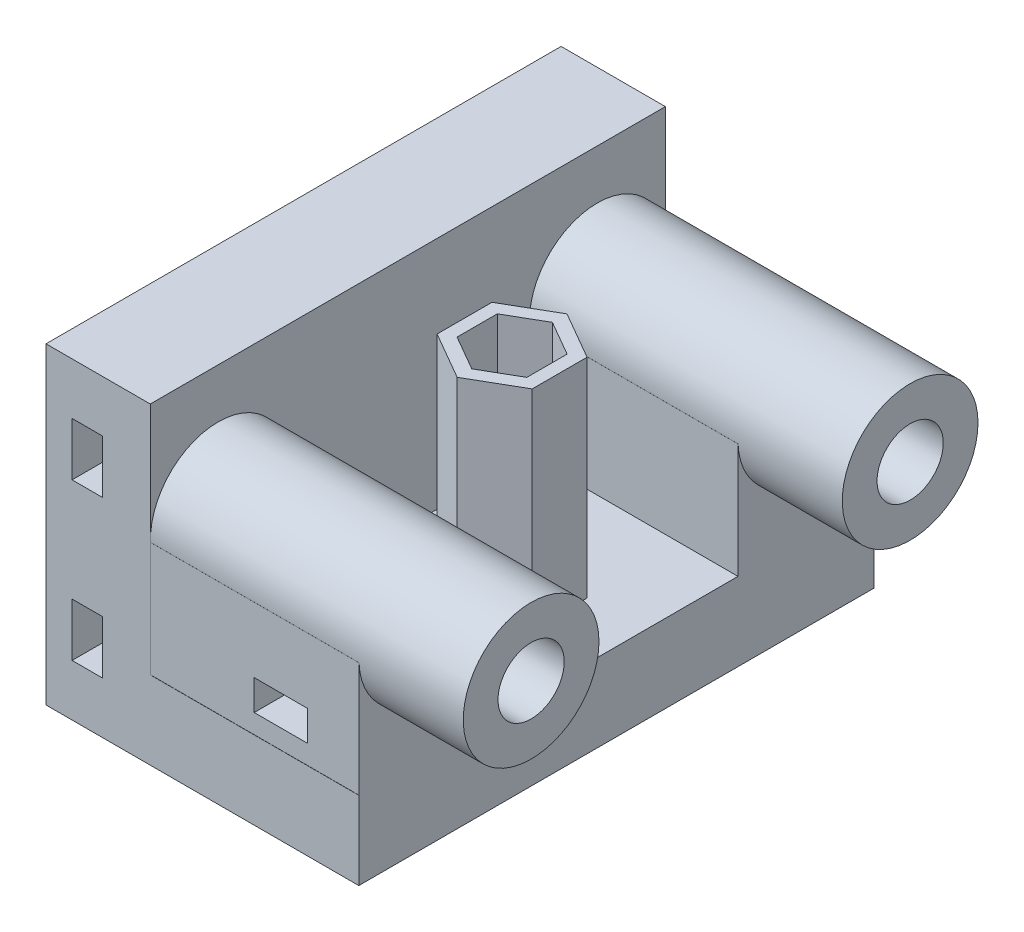
SolidWorks part; units mm, degrees
ref_plane "Front Plane" through (0, 0, 0) normal (0, 0, 1) x (1, 0, 0)
ref_plane "Top Plane" through (0, 0, 0) normal (0, 1, 0) x (1, 0, 0)
ref_plane "Right Plane" through (0, 0, 0) normal (1, 0, 0) x (0, 0, -1)
sketch "Sketch1" plane through (0, 0, 0) normal (1, 0, 0) x (0, 0, -1)
  line L1 (0, 0) -> (88.9, 0)
  line L2 (0, 0) -> (0, 76.2)
  line L3 (0, 76.2) -> (88.9, 76.2)
  line L4 (88.9, 0) -> (88.9, 76.2)
  dimension "D1" = 76.2
  dimension "D2" = 88.9
extrude "Boss-Extrude1" add sketch "Sketch1" along normal blind 25.4
sketch "Sketch2" plane through (0, 0, 0) normal (-1, 0, 0) x (0, 0, 1)
  line L0 (-88.9, 0) -> (-88.9, 76.2) construction
  line L1 (-80.264, 19.05) -> (-88.9, 19.05) construction
  line L2 (-80.264, 57.15) -> (-88.9, 57.15) construction
  line L3 (-44.45, 76.2) -> (-44.45, 0) construction
  line L4 (-88.9, 76.2) -> (0, 76.2) construction
  line L5 (0, 0) -> (-88.9, 0) construction
  circle A0 centre (-80.264, 57.15) radius 4.1021
  circle A1 centre (-80.264, 19.05) radius 4.1021
  circle A2 centre (-8.636, 19.05) radius 4.1021
  circle A3 centre (-8.636, 57.15) radius 4.1021
  dimension "D2" = 8.2042
  dimension "d1" = 19.05
  dimension "D3" = 8.636
  dimension "D4" = 38.1
extrude "Cut-Extrude1" cut sketch "Sketch2" against normal blind 19.05 contours A1 | A3 | A2 | A0 region at (0, 19.05, -80.264) region at (0, 19.05, -8.636) region at (0, 57.15, -8.636)
sketch "Sketch3" plane through (0, 0, 0) normal (0, 0, 1) x (1, 0, 0)
  line L0 (0, 61.2521) -> (0, 53.0479) construction
  line L1 (0, 57.15) -> (13.716, 57.15) construction
  line L2 (6.35, 63.627) -> (13.716, 63.627)
  line L3 (6.35, 63.627) -> (6.35, 50.673)
  line L4 (6.35, 50.673) -> (13.716, 50.673)
  line L5 (0, 38.1) -> (25.4, 38.1) construction
  line L6 (0, 76.2) -> (0, 0) construction
  line L7 (25.4, 76.2) -> (25.4, 0) construction
  line L8 (13.716, 12.573) -> (13.716, 25.527)
  line L9 (0, 61.2521) -> (0, 53.0479)
  line L11 (6.35, 25.527) -> (13.716, 25.527)
  line L12 (13.716, 63.627) -> (13.716, 50.673)
  line L13 (6.35, 12.573) -> (6.35, 25.527)
  line L14 (6.35, 12.573) -> (13.716, 12.573)
  dimension "D1" = 7.366
  dimension "D2" = 12.954
  dimension "D3" = 6.35
extrude "Cut-Extrude2" cut sketch "Sketch3" against normal blind 15.24 contours L12 L2 L3 L4 | L13 L14 L8 L11 region at (10.033, 57.15, 0) region at (10.033, 19.05, 0)
ref_plane "Plane1" through (0, 0, -44.45) normal (0, 0, 1) x (1, 0, 0)
mirror "Mirror1" about plane through (0, 0, -44.45) normal (0, 0, 1) of "Cut-Extrude2"
sketch "Sketch5" plane through (25.4, 0, 0) normal (1, 0, 0) x (0, 0, -1)
  line L0 (88.9, 0) -> (88.9, 76.2) construction
  line L1 (0, 0) -> (88.9, 0)
  line L2 (0, 0) -> (0, 19.05)
  line L3 (0, 19.05) -> (88.9, 19.05)
  line L4 (88.9, 0) -> (88.9, 19.05)
  dimension "D1" = 19.05
extrude "Boss-Extrude2" add sketch "Sketch5" along normal blind 50.8
sketch "Sketch6" plane through (25.4, 0, 0) normal (1, 0, 0) x (0, 0, -1)
  line L0 (-1.7145, 47.625) -> (90.6145, 47.625) construction
  line L3 (44.45, 76.2) -> (44.45, 19.05) construction
  line L4 (88.9, 76.2) -> (0, 76.2) construction
  line L5 (88.9, 19.05) -> (0, 19.05) construction
  line L6 (-1.7145, 47.625) -> (-1.7145, 64.1562) construction
  circle A0 centre (-1.7145, 47.625) radius 8.0645
  circle A1 centre (-1.7145, 47.625) radius 16.5312
  circle A2 centre (90.6145, 47.625) radius 8.0645
  circle A3 centre (90.6145, 47.625) radius 16.5312
  point P8 (44.45, 47.625)
  point P9 (44.45, 47.625)
  dimension "D2" = 16.129
  dimension "D3" = 8.4667
  dimension "D5" = 33.0623
  dimension "D4" = 16.5312
  dimension "V2" = 92.329
extrude "Boss-Extrude3" add sketch "Sketch6" along normal blind 76.2
sketch "Sketch7" plane through (0, 0, 0) normal (0, 0, 1) x (1, 0, 0)
  line L0 (25.4, 19.05) -> (25.4, 0)
  line L9 (25.4, 31.183) -> (25.4, 39.7449)
  line L10 (0, 76.2) -> (0, 0)
  line L11 (0, 0) -> (76.2, 0)
  line L12 (76.2, 0) -> (76.2, 19.05)
  line L13 (76.2, 19.05) -> (25.4, 19.05)
  line L14 (25.4, 19.05) -> (25.4, 31.183)
  line L15 (25.4, 31.183) -> (25.4, 39.7449)
  line L16 (25.4, 39.7449) -> (25.4, 55.5051)
  line L17 (25.4, 39.7449) -> (25.4, 55.5051)
  line L19 (25.4, 76.2) -> (0, 76.2)
  line L20 (0, 76.2) -> (0, 0)
  line L21 (0, 0) -> (76.2, 0)
  line L22 (76.2, 0) -> (76.2, 19.05)
  line L23 (76.2, 19.05) -> (25.4, 19.05)
  line L24 (25.4, 19.05) -> (25.4, 31.183)
  line L26 (25.4, 55.5051) -> (25.4, 64.067)
  line L27 (25.4, 55.5051) -> (25.4, 64.067)
  line L28 (25.4, 64.067) -> (25.4, 76.2)
  line L29 (25.4, 76.2) -> (0, 76.2)
  line L30 (25.4, 64.067) -> (25.4, 76.2)
  line M11 (13.716, 63.627) -> (13.716, 50.673)
  line M12 (13.716, 50.673) -> (6.35, 50.673)
  line M13 (6.35, 50.673) -> (6.35, 63.627)
  line M14 (6.35, 63.627) -> (13.716, 63.627)
  line M15 (0, 76.2) -> (0, 0)
  line M16 (0, 0) -> (76.2, 0)
  line M17 (76.2, 0) -> (76.2, 19.05)
  line M18 (76.2, 19.05) -> (25.4, 19.05)
  line M19 (25.4, 19.05) -> (25.4, 31.183)
  line M20 (25.4, 31.183) -> (25.4, 39.7449)
  line M21 (25.4, 39.7449) -> (25.4, 55.5051)
  line M22 (25.4, 55.5051) -> (25.4, 64.067)
  line M23 (25.4, 64.067) -> (25.4, 76.2)
  line M24 (25.4, 76.2) -> (0, 76.2)
  line M25 (6.35, 12.573) -> (6.35, 25.527)
  line M26 (6.35, 25.527) -> (13.716, 25.527)
  line M27 (13.716, 25.527) -> (13.716, 12.573)
  line M28 (13.716, 12.573) -> (6.35, 12.573)
  dimension "D1" = 0
extrude "Boss-Extrude4" add sketch "Sketch7" along normal blind 18.288 contours L0 M18 M16 M17 | L0 M19 M20 M21 M22 M23 M24 M15 M16 M28 M25 M26 M27 M14 M11 M12 M13 region at (50.8, 9.525, 0) region at (12.9917, 38.1, 0)
mirror "Mirror2" about plane through (0, 0, -44.45) normal (0, 0, 1) of "Boss-Extrude4"
sketch "Sketch8" plane through (0, 19.05, 0) normal (0, 1, 0) x (1, 0, 0)
  line L0 (101.6, 14.8167) -> (25.4, 14.8167) construction
  line L1 (25.4, -18.2457) -> (101.6, -18.2457) construction
  line L2 (101.6, 14.8167) -> (25.4, 14.8167)
  line L3 (25.4, -18.2457) -> (101.6, -18.2457)
  line L4 (25.4, 107.188) -> (25.4, -18.288)
  line L5 (25.4, -18.288) -> (76.2, -18.288)
  line L6 (76.2, -18.288) -> (76.2, 107.188)
  line L7 (76.2, 107.188) -> (25.4, 107.188)
  line L8 (25.4, 107.188) -> (25.4, -18.288)
  line L9 (25.4, -18.288) -> (76.2, -18.288)
  line L10 (76.2, -18.288) -> (76.2, 107.188)
  line L11 (76.2, 107.188) -> (25.4, 107.188)
  line L13 (25.4, 14.8167) -> (76.2, 14.8167)
  line L14 (25.4, 14.8167) -> (25.4, -18.2457)
  line L15 (25.4, -18.2457) -> (76.2, -18.2457)
  line L16 (76.2, 14.8167) -> (76.2, -18.2457)
  line M5 (25.4, 107.188) -> (25.4, -18.288)
  line M7 (76.2, -18.288) -> (76.2, 107.188)
  dimension "D1" = 0
extrude "Boss-Extrude5" add sketch "Sketch8" along normal blind 27.94 contours L3 L2 M5 M7 region at (50.8, 19.05, 1.7145)
sketch "Sketch11" plane through (101.6, 0, 0) normal (1, 0, 0) x (0, 0, -1)
  circle A0 centre (-1.7145, 47.625) radius 8.0645
  circle A1 centre (-1.7145, 47.625) radius 8.0645 construction
extrude "Cut-Extrude5" cut sketch "Sketch11" against normal blind 76.2
sketch "Sketch12" plane through (0, 0, 0) normal (0, -1, 0) x (1, 0, 0)
  line L0 (101.6, -6.35) -> (101.6, 9.779) construction
  line L1 (101.6, -6.35) -> (101.6, 9.779)
  line L2 (101.6, 1.7145) -> (0, 1.7145) construction
  line L3 (0, 18.288) -> (0, -107.188) construction
  line L4 (76.2, -14.8045) -> (76.2, 18.2335) construction
  line L5 (0, 18.288) -> (76.2, 18.288) construction
  line L6 (57.15, -2.3876) -> (57.15, 18.288) construction
  circle A0 centre (57.15, 1.7145) radius 4.1021
  dimension "D2" = 8.2042
  dimension "D3" = 20.6756
  dimension "D1" = 19.05
extrude "Cut-Extrude6" cut sketch "Sketch12" against normal up to next contours L2 A0 | A0 L2 region at (57.15, 0, 1.7145)
sketch "Sketch13" plane through (0, 0, 18.2457) normal (0, 0, 1) x (1, 0, 0)
  line L0 (53.0479, 0) -> (61.2521, 0) construction
  line L1 (53.0479, 0) -> (61.2521, 0)
  line L2 (57.15, 0) -> (57.15, 46.99) construction
  line L3 (25.4, 46.99) -> (76.2, 46.99) construction
  line L4 (76.2, 31.0938) -> (101.6, 31.0938) construction
  line L5 (76.2, 31.0938) -> (101.6, 31.0938)
  line L7 (50.673, 31.0938) -> (63.627, 31.0938)
  line L8 (50.673, 31.0938) -> (50.673, 23.7278)
  line L9 (50.673, 23.7278) -> (63.627, 23.7278)
  line L10 (63.627, 31.0938) -> (63.627, 23.7278)
  point P12 (57.15, 31.0938)
  dimension "D1" = 7.366
  dimension "D2" = 12.954
extrude "Cut-Extrude7" cut sketch "Sketch13" against normal blind 22.9616 contours L2 L9 L10 L7 | L9 L2 L7 L8 region at (53.9115, 27.4108, 18.2457) region at (60.3885, 27.4108, 18.2457)
mirror "Mirror3" about plane through (0, 0, -44.45) normal (0, 0, 1) of "Cut-Extrude7", "Cut-Extrude6", "Boss-Extrude5", "Cut-Extrude5"
sketch "Sketch14" plane through (0, 19.05, 0) normal (0, 1, 0) x (1, 0, 0)
  line L0 (25.4, 44.45) -> (76.2, 44.45) construction
  line L1 (25.4, 74.0833) -> (25.4, 14.8167) construction
  line L2 (76.2, 74.0833) -> (76.2, 14.8167) construction
  line L3 (50.8, 31.0767) -> (59.3, 39.5425) construction
  line L4 (42.3, 39.5425) -> (50.8, 34.635)
  line L5 (50.8, 34.635) -> (59.3, 39.5425)
  line L6 (59.3, 39.5425) -> (59.3, 49.3575)
  line L7 (59.3, 49.3575) -> (50.8, 54.265)
  line L8 (50.8, 54.265) -> (42.3, 49.3575)
  line L9 (42.3, 49.3575) -> (42.3, 39.5425)
  line L10 (50.8, 57.8233) -> (39.2184, 51.1366)
  line L11 (39.2184, 51.1366) -> (39.2184, 37.7634)
  line L12 (39.2184, 37.7634) -> (50.8, 31.0767)
  line L13 (50.8, 31.0767) -> (62.3816, 37.7634)
  line L14 (62.3816, 37.7634) -> (62.3816, 51.1366)
  line L15 (62.3816, 51.1366) -> (50.8, 57.8233)
  circle A0 centre (50.8, 44.45) radius 8.5 construction
  circle A1 centre (50.8, 44.45) radius 11.5816 construction
  circle A2 centre (50.8, 44.45) radius 5.25
  dimension "D2" = 10.5
  dimension "D1" = 17
  dimension "D3" = 8.4658
extrude "Boss-Extrude6" add sketch "Sketch14" along normal blind 50.8 contours L14 L15 L10 L11 L12 L13 L9 L8 L7 L6 L5 L4 region at (56.4139, 19.05, -54.1736)
extrude "Cut-Extrude8" cut sketch "Sketch14<3>" against normal up to next contours A2 region at (50.8, 19.05, -44.45)
sketch "Sketch14<3>" plane through (0, 19.05, 0) normal (0, 1, 0) x (1, 0, 0) same geometry as "Sketch14"
sketch "Sketch15" plane through (0, 0, 0) normal (0, -1, 0) x (1, 0, 0)
  line L1 (59.35, -39.5137) -> (50.8, -34.5773)
  line L2 (50.8, -34.5773) -> (42.25, -39.5137)
  line L3 (42.25, -39.5137) -> (42.25, -49.3863)
  line L4 (42.25, -49.3863) -> (50.8, -54.3227)
  line L5 (50.8, -54.3227) -> (59.35, -49.3863)
  line L6 (59.35, -49.3863) -> (59.35, -39.5137)
  circle A0 centre (50.8, -44.45) radius 8.55 construction
  dimension "D1" = 17.1
extrude "Cut-Extrude9" cut sketch "Sketch15" against normal blind 9
equation "\"d1\"= 0.75"
equation "\"d1@Sketch2\"  = \"d1\""
equation "\"V1\"= \"D2@Sketch6\""
equation "\"V2\"= \"V1\" + 3"
